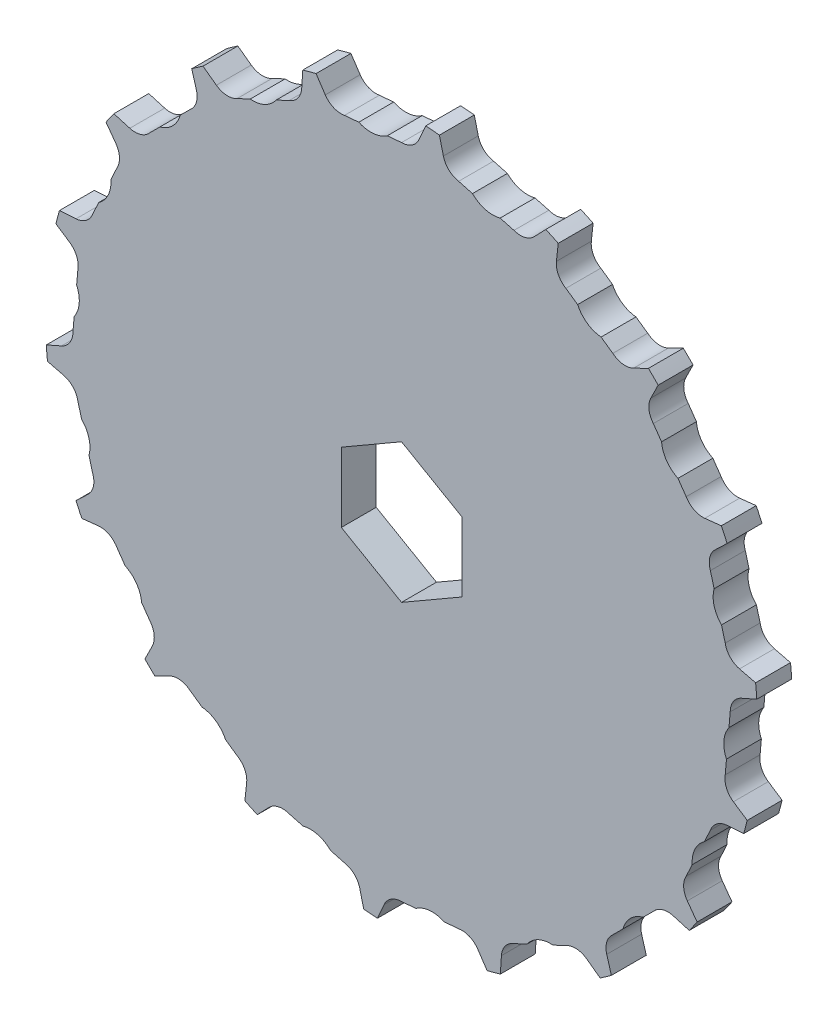
SolidWorks part; units mm, degrees
ref_plane "Front Plane" through (0, 0, 0) normal (0, 0, 1) x (1, 0, 0)
ref_plane "Top Plane" through (0, 0, 0) normal (0, 1, 0) x (1, 0, 0)
ref_plane "Right Plane" through (0, 0, 0) normal (1, 0, 0) x (0, 0, -1)
sketch "Sketch1" plane through (0, 0, 0) normal (0, 0, 1) x (1, 0, 0)
  line L0 (3.6596, 71.1503) -> (5.6741, 75.716)
  line L1 (3.6596, 71.1503) -> (8.7511, 70.7049) construction
  line L2 (7.5601, 75.551) -> (8.7511, 70.7049)
  line L3 (3.6596, 71.1503) -> (0, 0) construction
  line L4 (0, 0) -> (8.7511, 70.7049) construction
  line L5 (15.9591, 69.4339) -> (18.7358, 73.5804)
  line L6 (20.5645, 73.0904) -> (20.8959, 68.1111)
  line L7 (27.7738, 65.6078) -> (31.2283, 69.2091)
  line L8 (32.9441, 68.409) -> (32.4058, 63.4478)
  line L9 (38.7445, 59.7882) -> (42.7719, 62.7349)
  line L10 (44.3227, 61.649) -> (42.9311, 56.8567)
  line L11 (48.538, 52.1519) -> (53.0159, 54.3546)
  line L12 (54.3546, 53.0159) -> (52.1519, 48.538)
  line L13 (56.8567, 42.9311) -> (61.649, 44.3227)
  line L14 (62.7349, 42.7719) -> (59.7882, 38.7445)
  line L15 (63.4478, 32.4058) -> (68.409, 32.9441)
  line L16 (69.2091, 31.2283) -> (65.6078, 27.7738)
  line L17 (68.1111, 20.8959) -> (73.0904, 20.5645)
  line L18 (73.5804, 18.7358) -> (69.4339, 15.9591)
  line L19 (70.7049, 8.7511) -> (75.551, 7.5601)
  line L20 (75.716, 5.6741) -> (71.1503, 3.6596)
  line L21 (71.1503, -3.6596) -> (75.716, -5.6741)
  line L22 (75.551, -7.5601) -> (70.7049, -8.7511)
  line L23 (69.4339, -15.9591) -> (73.5804, -18.7358)
  line L24 (73.0904, -20.5645) -> (68.1111, -20.8959)
  line L25 (65.6078, -27.7738) -> (69.2091, -31.2283)
  line L26 (68.409, -32.9441) -> (63.4478, -32.4058)
  line L27 (59.7882, -38.7445) -> (62.7349, -42.7719)
  line L28 (61.649, -44.3227) -> (56.8567, -42.9311)
  line L29 (52.1519, -48.538) -> (54.3546, -53.0159)
  line L30 (53.0159, -54.3546) -> (48.538, -52.1519)
  line L31 (42.9311, -56.8567) -> (44.3227, -61.649)
  line L32 (42.7719, -62.7349) -> (38.7445, -59.7882)
  line L33 (32.4058, -63.4478) -> (32.9441, -68.409)
  line L34 (31.2283, -69.2091) -> (27.7738, -65.6078)
  line L35 (20.8959, -68.1111) -> (20.5645, -73.0904)
  line L36 (18.7358, -73.5804) -> (15.9591, -69.4339)
  line L37 (8.7511, -70.7049) -> (7.5601, -75.551)
  line L38 (5.6741, -75.716) -> (3.6596, -71.1503)
  line L39 (-3.6596, -71.1503) -> (-5.6741, -75.716)
  line L40 (-7.5601, -75.551) -> (-8.7511, -70.7049)
  line L41 (-15.9591, -69.4339) -> (-18.7358, -73.5804)
  line L42 (-20.5645, -73.0904) -> (-20.8959, -68.1111)
  line L43 (-27.7738, -65.6078) -> (-31.2283, -69.2091)
  line L44 (-32.9441, -68.409) -> (-32.4058, -63.4478)
  line L45 (-38.7445, -59.7882) -> (-42.7719, -62.7349)
  line L46 (-44.3227, -61.649) -> (-42.9311, -56.8567)
  line L47 (-48.538, -52.1519) -> (-53.0159, -54.3546)
  line L48 (-54.3546, -53.0159) -> (-52.1519, -48.538)
  line L49 (-56.8567, -42.9311) -> (-61.649, -44.3227)
  line L50 (-62.7349, -42.7719) -> (-59.7882, -38.7445)
  line L51 (-63.4478, -32.4058) -> (-68.409, -32.9441)
  line L52 (-69.2091, -31.2283) -> (-65.6078, -27.7738)
  line L53 (-68.1111, -20.8959) -> (-73.0904, -20.5645)
  line L54 (-73.5804, -18.7358) -> (-69.4339, -15.9591)
  line L55 (-70.7049, -8.7511) -> (-75.551, -7.5601)
  line L56 (-75.716, -5.6741) -> (-71.1503, -3.6596)
  line L57 (-71.1503, 3.6596) -> (-75.716, 5.6741)
  line L58 (-75.551, 7.5601) -> (-70.7049, 8.7511)
  line L59 (-69.4339, 15.9591) -> (-73.5804, 18.7358)
  line L60 (-73.0904, 20.5645) -> (-68.1111, 20.8959)
  line L61 (-65.6078, 27.7738) -> (-69.2091, 31.2283)
  line L62 (-68.409, 32.9441) -> (-63.4478, 32.4058)
  line L63 (-59.7882, 38.7445) -> (-62.7349, 42.7719)
  line L64 (-61.649, 44.3227) -> (-56.8567, 42.9311)
  line L65 (-52.1519, 48.538) -> (-54.3546, 53.0159)
  line L66 (-53.0159, 54.3546) -> (-48.538, 52.1519)
  line L67 (-42.9311, 56.8567) -> (-44.3227, 61.649)
  line L68 (-42.7719, 62.7349) -> (-38.7445, 59.7882)
  line L69 (-32.4058, 63.4478) -> (-32.9441, 68.409)
  line L70 (-31.2283, 69.2091) -> (-27.7738, 65.6078)
  line L71 (-20.8959, 68.1111) -> (-20.5645, 73.0904)
  line L72 (-18.7358, 73.5804) -> (-15.9591, 69.4339)
  line L73 (-8.7511, 70.7049) -> (-7.5601, 75.551)
  line L74 (-5.6741, 75.716) -> (-3.6596, 71.1503)
  line L83 (0, 72.765) -> (0, 0) construction
  line L84 (0, 0) -> (6.589, 75.3123) construction
  circle A0 centre (0, 0) radius 72.765 construction
  arc A1 (-3.9985, 72.6551) -> (3.6596, 71.1503) centre (0, 72.765) ccw
  arc A2 (4.3155, 72.6369) -> (8.3633, 72.2828) centre (0, 0) cw
  arc A3 (5.6741, 75.716) -> (7.5601, 75.551) centre (6.589, 75.3123) cw
  arc A4 (8.6787, 72.2456) -> (15.9591, 69.4339) centre (12.6355, 71.6595) ccw
  arc A5 (18.7358, 73.5804) -> (20.5645, 73.0904) centre (19.5667, 73.024) cw
  arc A6 (21.0921, 69.641) -> (27.7738, 65.6078) centre (24.8871, 68.3767) ccw
  arc A7 (31.2283, 69.2091) -> (32.9441, 68.409) centre (31.9499, 68.5169) cw
  arc A8 (32.8647, 64.9204) -> (38.7445, 59.7882) centre (36.3825, 63.0163) ccw
  arc A9 (42.7719, 62.7349) -> (44.3227, 61.649) centre (43.3624, 61.9279) cw
  arc A10 (43.6388, 58.2272) -> (48.538, 52.1519) centre (46.7724, 55.7412) ccw
  arc A11 (53.0159, 54.3546) -> (54.3546, 53.0159) centre (53.4573, 53.4573) cw
  arc A12 (53.0868, 49.7648) -> (56.8567, 42.9311) centre (55.7412, 46.7724) ccw
  arc A13 (61.649, 44.3227) -> (62.7349, 42.7719) centre (61.9279, 43.3624) cw
  arc A14 (60.9219, 39.7903) -> (63.4478, 32.4058) centre (63.0163, 36.3825) ccw
  arc A15 (68.409, 32.9441) -> (69.2091, 31.2283) centre (68.5169, 31.9499) cw
  arc A16 (66.9059, 28.6068) -> (68.1111, 20.8959) centre (68.3767, 24.8871) ccw
  arc A17 (73.0904, 20.5645) -> (73.5804, 18.7358) centre (73.024, 19.5667) cw
  arc A18 (70.8569, 16.5542) -> (70.7049, 8.7511) centre (71.6595, 12.6355) ccw
  arc A19 (75.551, 7.5601) -> (75.716, 5.6741) centre (75.3123, 6.589) cw
  arc A20 (72.6551, 3.9985) -> (71.1503, -3.6596) centre (72.765, 0) ccw
  arc A21 (75.716, -5.6741) -> (75.551, -7.5601) centre (75.3123, -6.589) cw
  arc A22 (72.2456, -8.6787) -> (69.4339, -15.9591) centre (71.6595, -12.6355) ccw
  arc A23 (73.5804, -18.7358) -> (73.0904, -20.5645) centre (73.024, -19.5667) cw
  arc A24 (69.641, -21.0921) -> (65.6078, -27.7738) centre (68.3767, -24.8871) ccw
  arc A25 (69.2091, -31.2283) -> (68.409, -32.9441) centre (68.5169, -31.9499) cw
  arc A26 (64.9204, -32.8647) -> (59.7882, -38.7445) centre (63.0163, -36.3825) ccw
  arc A27 (62.7349, -42.7719) -> (61.649, -44.3227) centre (61.9279, -43.3624) cw
  arc A28 (58.2272, -43.6388) -> (52.1519, -48.538) centre (55.7412, -46.7724) ccw
  arc A29 (54.3546, -53.0159) -> (53.0159, -54.3546) centre (53.4573, -53.4573) cw
  arc A30 (49.7648, -53.0868) -> (42.9311, -56.8567) centre (46.7724, -55.7412) ccw
  arc A31 (44.3227, -61.649) -> (42.7719, -62.7349) centre (43.3624, -61.9279) cw
  arc A32 (39.7903, -60.9219) -> (32.4058, -63.4478) centre (36.3825, -63.0163) ccw
  arc A33 (32.9441, -68.409) -> (31.2283, -69.2091) centre (31.9499, -68.5169) cw
  arc A34 (28.6068, -66.9059) -> (20.8959, -68.1111) centre (24.8871, -68.3767) ccw
  arc A35 (20.5645, -73.0904) -> (18.7358, -73.5804) centre (19.5667, -73.024) cw
  arc A36 (16.5542, -70.8569) -> (8.7511, -70.7049) centre (12.6355, -71.6595) ccw
  arc A37 (7.5601, -75.551) -> (5.6741, -75.716) centre (6.589, -75.3123) cw
  arc A38 (3.9985, -72.6551) -> (-3.6596, -71.1503) centre (0, -72.765) ccw
  arc A39 (-5.6741, -75.716) -> (-7.5601, -75.551) centre (-6.589, -75.3123) cw
  arc A40 (-8.6787, -72.2456) -> (-15.9591, -69.4339) centre (-12.6355, -71.6595) ccw
  arc A41 (-18.7358, -73.5804) -> (-20.5645, -73.0904) centre (-19.5667, -73.024) cw
  arc A42 (-21.0921, -69.641) -> (-27.7738, -65.6078) centre (-24.8871, -68.3767) ccw
  arc A43 (-31.2283, -69.2091) -> (-32.9441, -68.409) centre (-31.9499, -68.5169) cw
  arc A44 (-32.8647, -64.9204) -> (-38.7445, -59.7882) centre (-36.3825, -63.0163) ccw
  arc A45 (-42.7719, -62.7349) -> (-44.3227, -61.649) centre (-43.3624, -61.9279) cw
  arc A46 (-43.6388, -58.2272) -> (-48.538, -52.1519) centre (-46.7724, -55.7412) ccw
  arc A47 (-53.0159, -54.3546) -> (-54.3546, -53.0159) centre (-53.4573, -53.4573) cw
  arc A48 (-53.0868, -49.7648) -> (-56.8567, -42.9311) centre (-55.7412, -46.7724) ccw
  arc A49 (-61.649, -44.3227) -> (-62.7349, -42.7719) centre (-61.9279, -43.3624) cw
  arc A50 (-60.9219, -39.7903) -> (-63.4478, -32.4058) centre (-63.0163, -36.3825) ccw
  arc A51 (-68.409, -32.9441) -> (-69.2091, -31.2283) centre (-68.5169, -31.9499) cw
  arc A52 (-66.9059, -28.6068) -> (-68.1111, -20.8959) centre (-68.3767, -24.8871) ccw
  arc A53 (-73.0904, -20.5645) -> (-73.5804, -18.7358) centre (-73.024, -19.5667) cw
  arc A54 (-70.8569, -16.5542) -> (-70.7049, -8.7511) centre (-71.6595, -12.6355) ccw
  arc A55 (-75.551, -7.5601) -> (-75.716, -5.6741) centre (-75.3123, -6.589) cw
  arc A56 (-72.6551, -3.9985) -> (-71.1503, 3.6596) centre (-72.765, 0) ccw
  arc A57 (-75.716, 5.6741) -> (-75.551, 7.5601) centre (-75.3123, 6.589) cw
  arc A58 (-72.2456, 8.6787) -> (-69.4339, 15.9591) centre (-71.6595, 12.6355) ccw
  arc A59 (-73.5804, 18.7358) -> (-73.0904, 20.5645) centre (-73.024, 19.5667) cw
  arc A60 (-69.641, 21.0921) -> (-65.6078, 27.7738) centre (-68.3767, 24.8871) ccw
  arc A61 (-69.2091, 31.2283) -> (-68.409, 32.9441) centre (-68.5169, 31.9499) cw
  arc A62 (-64.9204, 32.8647) -> (-59.7882, 38.7445) centre (-63.0163, 36.3825) ccw
  arc A63 (-62.7349, 42.7719) -> (-61.649, 44.3227) centre (-61.9279, 43.3624) cw
  arc A64 (-58.2272, 43.6388) -> (-52.1519, 48.538) centre (-55.7412, 46.7724) ccw
  arc A65 (-54.3546, 53.0159) -> (-53.0159, 54.3546) centre (-53.4573, 53.4573) cw
  arc A66 (-49.7648, 53.0868) -> (-42.9311, 56.8567) centre (-46.7724, 55.7412) ccw
  arc A67 (-44.3227, 61.649) -> (-42.7719, 62.7349) centre (-43.3624, 61.9279) cw
  arc A68 (-39.7903, 60.9219) -> (-32.4058, 63.4478) centre (-36.3825, 63.0163) ccw
  arc A69 (-32.9441, 68.409) -> (-31.2283, 69.2091) centre (-31.9499, 68.5169) cw
  arc A70 (-28.6068, 66.9059) -> (-20.8959, 68.1111) centre (-24.8871, 68.3767) ccw
  arc A71 (-20.5645, 73.0904) -> (-18.7358, 73.5804) centre (-19.5667, 73.024) cw
  arc A72 (-16.5542, 70.8569) -> (-8.7511, 70.7049) centre (-12.6355, 71.6595) ccw
  arc A73 (-7.5601, 75.551) -> (-5.6741, 75.716) centre (-6.589, 75.3123) cw
  point P289 (0, 0)
  dimension "D1" = 145.53
  dimension "D2" = 4
  dimension "D5" = 1
  dimension "D6" = 75.6
  dimension "D3" = 5
  dimension "D4" = 36
extrude "Boss-Extrude1" add sketch "Sketch1" along normal blind 7.3 contours L74 A73 L73 A72 L72 A71 L71 A70 L70 A69 L69 A68 L68 A67 L67 A66 L66 A65 L65 A64 L64 A63 L63 A62 L62 A61 L61 A60 L60 A59 L59 A58 L58 A57 L57 A56 | A3 L0 A2 L2 region at (-0.0042, -0.0476, 0) region at (6.4786, 74.0508, 0)
sketch "Sketch2" plane through (0, 0, 7.3) normal (0, 0, 1) x (1, 0, 0)
  circle A0 centre (0, 0) radius 12.5
  dimension "D1" = 25
extrude "Boss-Extrude2" add sketch "Sketch2" along normal blind 40
sketch "Sketch5" plane through (0, 0, 0) normal (0, 0, -1) x (-1, 0, 0)
  line L0 (0, 68.765) -> (2.9886, 68.5035)
  line L1 (0, 68.765) -> (0.7057, 76.8309)
  line L2 (11.9409, 67.7203) -> (12.6466, 75.7862)
  line L3 (0.7057, 76.8309) -> (12.6466, 75.7862)
  line L4 (8.9523, 67.9818) -> (11.9409, 67.7203)
  arc A0 (2.9886, 68.5035) -> (8.9523, 67.9818) centre (6.4237, 73.4229) ccw
  arc A3 (-3.6596, 71.1503) -> (3.6596, 71.1503) centre (0, 72.765) ccw construction
  arc A5 (-3.6596, 71.1503) -> (3.6596, 71.1503) centre (0, 72.765) ccw construction
  arc A7 (8.7511, 70.7049) -> (15.9591, 69.4339) centre (12.6355, 71.6595) ccw construction
  arc A8 (7.5601, 75.551) -> (5.6741, 75.716) centre (6.589, 75.3123) ccw construction
  point P19 (0, 68.765)
  point P22 (11.9409, 67.7203)
  dimension "D2" = 3
  dimension "D3" = 3
  dimension "D4" = 6
extrude "Cut-Extrude2" cut sketch "Sketch5" against normal blind 10
sketch "Sketch9" plane through (0, 0, 0) normal (0, 0, -1) x (-1, 0, 0)
  circle A0 centre (0, 0) radius 74.5
  circle A1 centre (0, 0) radius 100
  dimension "D1" = 149
  dimension "D2" = 200
extrude "Cut-Extrude5" cut sketch "Sketch9" against normal blind 10
fillet "Fillet1" radius 30 1 edges at (12.5, 0, 7.3)
sketch "Sketch3" plane through (0, 0, 47.3) normal (0, 0, 1) x (1, 0, 0)
  circle A0 centre (0, 0) radius 5
  dimension "D1" = 10
extrude "Cut-Extrude1" cut sketch "Sketch3" against normal through all
hole_wizard "Ø1.0mm Dowel Hole1" positions "3DSketch1" profile "Sketch4" hole size "Ø1.0" standard "ANSI Metric"
sketch3d "3DSketch1"
  point P0 (-6.8176, -10.4771, 42.0201)
  point P2 (-11.0684, 5.8086, 41.6583)
sketch "Sketch4" plane through (-6.8176, -10.4771, 42.0201) normal (0, 0, 1) x (0.8382, -0.5454, 0)
  line L0 (0, 0) -> (0, 34)
  line L1 (0, 34) -> (1.4, 33.1588)
  line L2 (1.4, 33.1588) -> (1.4, 0)
  line L5 (1.4, 0) -> (0, 0)
  line L10 (0, 34) -> (-1.4, 33.1588) construction
  line L11 (0, -6.35) -> (0, 107.95) construction
  dimension "Hole Dia." = 2.8
  dimension "Hole Depth" = 34
  dimension "Drill Angle" = 118
pattern_circular "CirPattern1" count 18 over 360 about axis through (0, 0, 0) along (0, 0, 1) of "Cut-Extrude2"
sketch "Sketch6" plane through (0, 0, 0) normal (0, 1, 0) x (1, 0, 0)
  line L1 (-74.3279, -7.3) -> (79.9055, -7.3)
  line L2 (-74.3279, -7.3) -> (-74.3279, -52.0573)
  line L3 (-74.3279, -52.0573) -> (79.9055, -52.0573)
  line L4 (79.9055, -7.3) -> (79.9055, -52.0573)
extrude "Cut-Extrude3" cut sketch "Sketch6" against normal through all both and the other way through all
sketch "Sketch7" plane through (0, 0, 0) normal (0, 0, -1) x (-1, 0, 0)
  line L1 (12.6, -7.2746) -> (12.6, 7.2746)
  line L2 (12.6, 7.2746) -> (0, 14.5492)
  line L3 (0, 14.5492) -> (-12.6, 7.2746)
  line L4 (-12.6, 7.2746) -> (-12.6, -7.2746)
  line L5 (-12.6, -7.2746) -> (0, -14.5492)
  line L6 (0, -14.5492) -> (12.6, -7.2746)
  circle A0 centre (0, 0) radius 12.6 construction
  dimension "D1" = 25.2
extrude "Cut-Extrude4" cut sketch "Sketch7" against normal through all both
equation "\"Teeth\"= 36"
equation "\"D4@Sketch1\"=\"Teeth\""
equation "\"D6@Sketch1\"=84/40*\"Teeth\""
equation "\"D1@Sketch1\"=161.70/40*\"Teeth\""
equation "\"D3@Sketch1\"=4.5/\"Teeth\"*40"
equation "\"D1@CirPattern1\"=\"Teeth\"/2"
